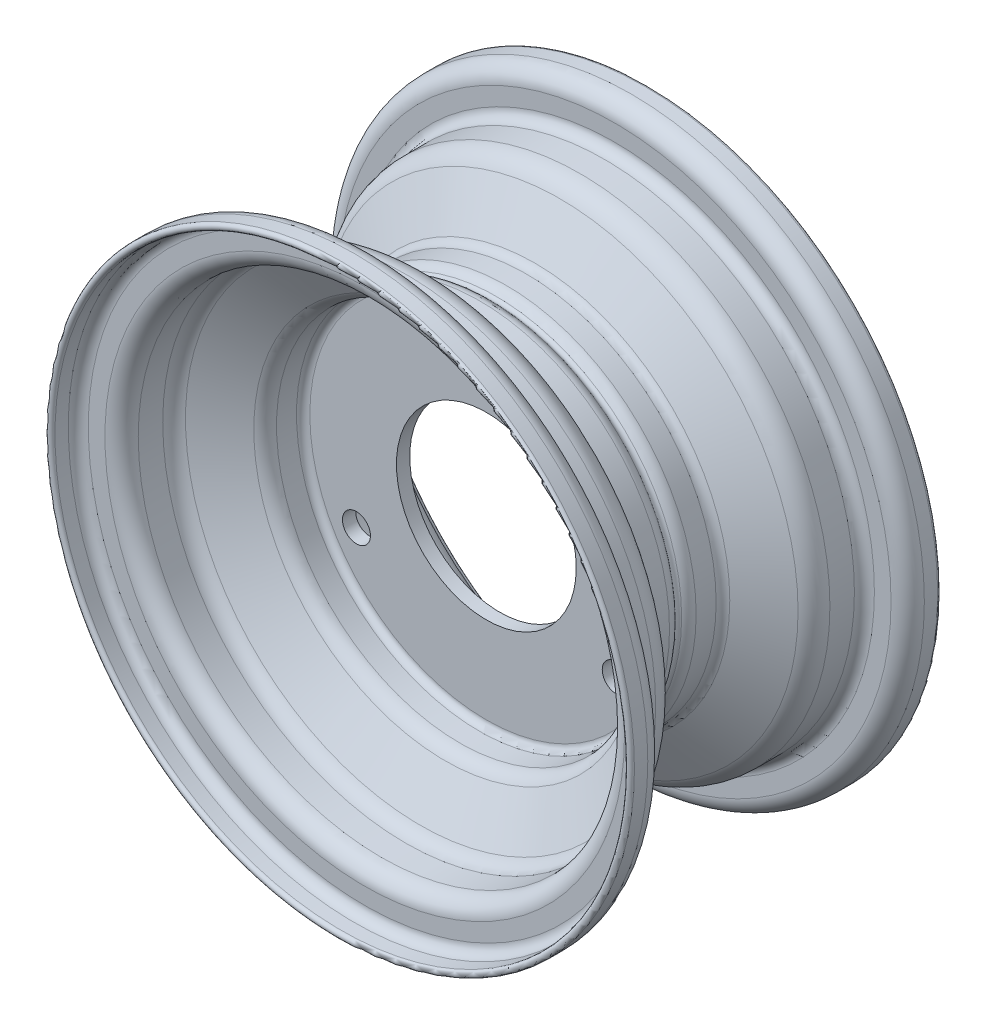
SolidWorks part; units mm, degrees
ref_plane "Plan de face" through (0, 0, 0) normal (0, 0, 1) x (1, 0, 0)
ref_plane "Plan de dessus" through (0, 0, 0) normal (0, 1, 0) x (1, 0, 0)
ref_plane "Plan de droite" through (0, 0, 0) normal (1, 0, 0) x (0, 0, -1)
sketch "Esquisse1" plane through (0, 0, 0) normal (1, 0, 0) x (0, 0, -1)
  line L0 (-10.1111, 0) -> (11.4899, 0) construction
  line L1 (0, 243.1553) -> (0, -10.029) construction
  line L2 (40.5355, 78) -> (35.2622, 78) construction
  line L3 (-71.7953, 185) -> (3.8081, 185) construction
  line L4 (-4, 55) -> (-10, 55)
  line L5 (2, 27) -> (-2, 27)
  line L6 (-2, 27) -> (-2, 53)
  line L7 (-14.3301, 57.5) -> (-21.8357, 70.5)
  line L8 (-26.1658, 73) -> (-33.5213, 73)
  line L9 (-38.5213, 78) -> (-38.5213, 83)
  line L10 (-41.5213, 86) -> (-45.5213, 86)
  line L11 (-45.5213, 88) -> (-41.5213, 88)
  line L12 (-36.5213, 83) -> (-36.5213, 78)
  line L13 (-43.0683, 83) -> (-33.2969, 83) construction
  line L14 (-33.5213, 75) -> (-26.1658, 75)
  line L15 (-40.5355, 78) -> (-35.2622, 78) construction
  line L16 (-10, 57) -> (-4, 57)
  line L17 (-20.1036, 71.5) -> (-12.5981, 58.5)
  line L18 (43.0683, 83) -> (33.2969, 83) construction
  line L19 (20.1036, 71.5) -> (12.5981, 58.5)
  line L20 (10, 57) -> (4, 57)
  line L21 (33.5213, 75) -> (26.1658, 75)
  line L22 (36.5213, 83) -> (36.5213, 78)
  line L23 (45.5213, 88) -> (41.5213, 88)
  line L24 (41.5213, 86) -> (45.5213, 86)
  line L25 (38.5213, 78) -> (38.5213, 83)
  line L26 (26.1658, 73) -> (33.5213, 73)
  line L27 (14.3301, 57.5) -> (21.8357, 70.5)
  line L28 (2, 27) -> (2, 53)
  line L29 (4, 55) -> (10, 55)
  arc A0 (-2, 53) -> (-4, 55) centre (-4, 53) ccw
  arc A1 (-10, 55) -> (-14.3301, 57.5) centre (-10, 60) cw
  arc A2 (-21.8357, 70.5) -> (-26.1658, 73) centre (-26.1658, 68) ccw
  arc A3 (-33.5213, 73) -> (-38.5213, 78) centre (-33.5213, 78) cw
  arc A4 (-38.5213, 83) -> (-41.5213, 86) centre (-41.5213, 83) ccw
  arc A5 (-41.5213, 88) -> (-36.5213, 83) centre (-41.5213, 83) cw
  arc A6 (-36.5213, 78) -> (-33.5213, 75) centre (-33.5213, 78) ccw
  arc A7 (-26.1658, 75) -> (-20.1036, 71.5) centre (-26.1658, 68) cw
  arc A8 (-12.5981, 58.5) -> (-10, 57) centre (-10, 60) ccw
  arc A9 (-45.5213, 88) -> (-45.5213, 86) centre (-45.5213, 87) ccw
  circle A10 centre (0, 128.4438) radius 56.5562 construction
  arc A11 (45.5213, 88) -> (45.5213, 86) centre (45.5213, 87) cw
  arc A12 (12.5981, 58.5) -> (10, 57) centre (10, 60) cw
  arc A13 (26.1658, 75) -> (20.1036, 71.5) centre (26.1658, 68) ccw
  arc A14 (36.5213, 78) -> (33.5213, 75) centre (33.5213, 78) cw
  arc A15 (41.5213, 88) -> (36.5213, 83) centre (41.5213, 83) ccw
  arc A16 (38.5213, 83) -> (41.5213, 86) centre (41.5213, 83) cw
  arc A17 (33.5213, 73) -> (38.5213, 78) centre (33.5213, 78) ccw
  arc A18 (21.8357, 70.5) -> (26.1658, 73) centre (26.1658, 68) cw
  arc A19 (10, 55) -> (14.3301, 57.5) centre (10, 60) ccw
  arc A20 (2, 53) -> (4, 55) centre (4, 53) cw
  arc A21 (-4, 57) -> (-1, 55.6458) centre (-4, 53) cw
  arc A22 (4, 57) -> (1, 55.6458) centre (4, 53) ccw
  arc A23 (-1, 55.6458) -> (1, 55.6458) centre (0, 56.5277) ccw
  point P76 (0, 27)
  dimension "D9" = 5
  dimension "D3" = 2
  dimension "D7" = 5
  dimension "D8" = 3
  dimension "D13" = 5
  dimension "D21" = 113.1123
  dimension "D2" = 185
  dimension "D4" = 2
  dimension "D5" = 27
  dimension "D6" = 30
  dimension "D10" = 18
  dimension "D11" = 31
  dimension "D12" = 55
  dimension "D14" = 36.5213
  dimension "D15" = 7
  dimension "D16" = 6
  dimension "D17" = 2
  dimension "D18" = 2
  dimension "D19" = 2
  dimension "D20" = 2
  dimension "D22" = 128.4438
revolve "Révolution1" add sketch "Esquisse1" angle 360 about L0
ref_axis "Axe1" through (0, 0, -2) along (0, 0, 1)
hole_wizard "Dégagement M81" positions "Esquisse3" profile "Esquisse2" hole size "M8" standard "ISO" end condition through all
sketch "Esquisse3" plane through (0, 0, -2) normal (0, 0, -1) x (-1, 0, 0)
  line L0 (0, 0) -> (0, 101.1332) construction
  circle A0 centre (0, 0) radius 45.0333 construction
  point P0 (0, 45.0333)
  point P2 (-39, -22.5167)
  point P4 (39, -22.5167)
  dimension "D1" = 78
  dimension "D2" = 78
  dimension "D3" = 78
sketch "Esquisse2" plane through (0, 45.0333, -2) normal (1, 0, 0) x (0, 1, 0)
  line L0 (0, 0) -> (0, 48.5213)
  line L1 (0, 48.5213) -> (4.2, 48.5213)
  line L2 (4.2, 48.5213) -> (4.2, 0)
  line L5 (4.2, 0) -> (0, 0)
  line L11 (0, -6.35) -> (0, 107.95) construction
  dimension "Diamètre du perçage jusqu'au prochain" = 8.4
  dimension "Profondeur du perçage jusqu'au prochain" = 48.5213
